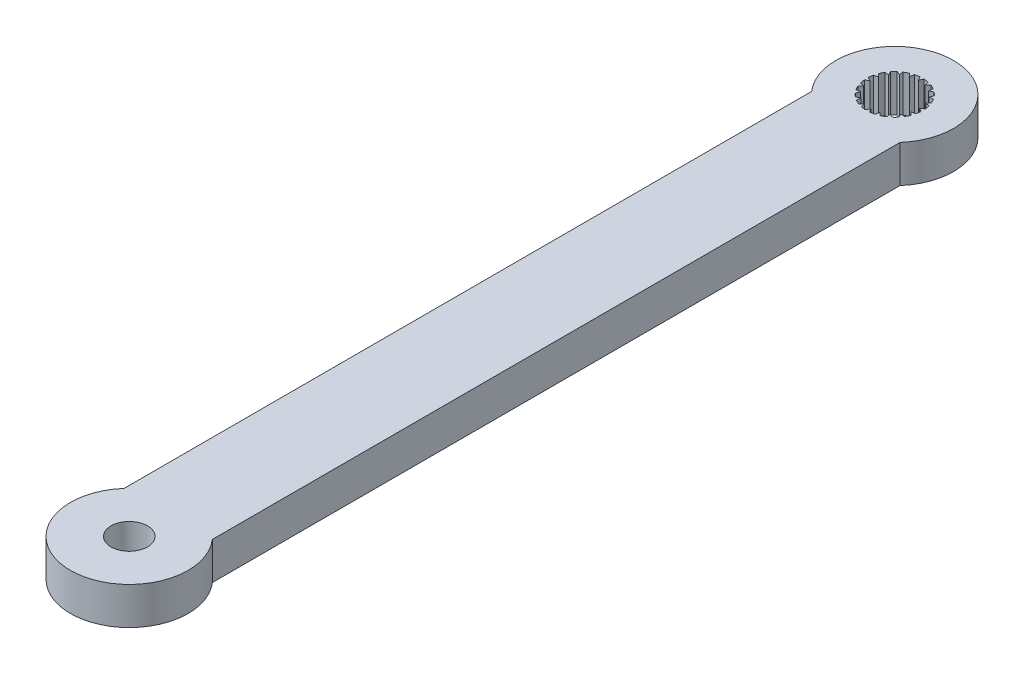
SolidWorks part; units mm, degrees
ref_plane "Front Plane" through (0, 0, 0) normal (0, 0, 1) x (1, 0, 0)
ref_plane "Top Plane" through (0, 0, 0) normal (0, 1, 0) x (1, 0, 0)
ref_plane "Right Plane" through (0, 0, 0) normal (1, 0, 0) x (0, 0, -1)
sketch "Sketch1" plane through (0, 0, 0) normal (0, 1, 0) x (1, 0, 0)
  line L1 (-3.75, -61.6928) -> (-3.75, -3.3072)
  line L4 (3.75, -61.6928) -> (3.75, -3.3072)
  line L5 (-3.75, -3.3072) -> (0, 0) construction
  line L6 (0, 0) -> (3.75, -3.3072) construction
  line L7 (-3.75, -3.3072) -> (3.75, -3.3072) construction
  line L48 (-1.178, -1.7007) -> (-1.2088, -2.0444)
  line L49 (-1.489, -1.8503) -> (-1.178, -1.7007)
  line L50 (-1.6459, -1.2535) -> (-1.7813, -1.5708)
  line L51 (-1.9879, -1.2996) -> (-1.6459, -1.2535)
  line L52 (-1.9527, -0.6835) -> (-2.1796, -0.9435)
  line L53 (-2.2922, -0.6217) -> (-1.9527, -0.6835)
  line L54 (-2.0684, -0.0466) -> (-2.3644, -0.2238)
  line L55 (-2.3721, 0.117) -> (-2.0684, -0.0466)
  line L56 (-1.9815, 0.5948) -> (-2.3179, 0.5178)
  line L57 (-2.2199, 0.8443) -> (-1.9815, 0.5948)
  line L58 (-1.7007, 1.178) -> (-2.0444, 1.2088)
  line L59 (-1.8503, 1.489) -> (-1.7007, 1.178)
  line L60 (-1.2535, 1.6459) -> (-1.5708, 1.7813)
  line L61 (-1.2996, 1.9879) -> (-1.2535, 1.6459)
  line L62 (-0.6835, 1.9527) -> (-0.9435, 2.1796)
  line L63 (-0.6217, 2.2922) -> (-0.6835, 1.9527)
  line L64 (-0.0466, 2.0684) -> (-0.2238, 2.3644)
  line L65 (0.117, 2.3721) -> (-0.0466, 2.0684)
  line L66 (0.5948, 1.9815) -> (0.5178, 2.3179)
  line L67 (0.8443, 2.2199) -> (0.5948, 1.9815)
  line L68 (1.178, 1.7007) -> (1.2088, 2.0444)
  line L69 (1.489, 1.8503) -> (1.178, 1.7007)
  line L70 (1.6459, 1.2535) -> (1.7813, 1.5708)
  line L71 (1.9879, 1.2996) -> (1.6459, 1.2535)
  line L72 (1.9527, 0.6835) -> (2.1796, 0.9435)
  line L73 (2.2922, 0.6217) -> (1.9527, 0.6835)
  line L74 (2.0684, 0.0466) -> (2.3644, 0.2238)
  line L75 (2.3721, -0.117) -> (2.0684, 0.0466)
  line L76 (1.9815, -0.5948) -> (2.3179, -0.5178)
  line L77 (2.2199, -0.8443) -> (1.9815, -0.5948)
  line L78 (1.7007, -1.178) -> (2.0444, -1.2088)
  line L79 (1.8503, -1.489) -> (1.7007, -1.178)
  line L80 (1.2535, -1.6459) -> (1.5708, -1.7813)
  line L81 (1.2996, -1.9879) -> (1.2535, -1.6459)
  line L82 (0.6835, -1.9527) -> (0.9435, -2.1796)
  line L83 (0.6217, -2.2922) -> (0.6835, -1.9527)
  line L84 (0.0466, -2.0684) -> (0.2238, -2.3644)
  line L85 (-0.117, -2.3721) -> (0.0466, -2.0684)
  line L86 (-0.5948, -1.9815) -> (-0.5178, -2.3179)
  line L87 (-0.8443, -2.2199) -> (-0.5948, -1.9815)
  line L88 (-1.178, -1.7007) -> (-1.2088, -2.0444)
  line L89 (-1.489, -1.8503) -> (-1.178, -1.7007)
  line L90 (-1.6459, -1.2535) -> (-1.7813, -1.5708)
  line L91 (-1.9879, -1.2996) -> (-1.6459, -1.2535)
  line L92 (-1.9527, -0.6835) -> (-2.1796, -0.9435)
  line L93 (-2.2922, -0.6217) -> (-1.9527, -0.6835)
  line L94 (-2.0684, -0.0466) -> (-2.3644, -0.2238)
  line L95 (-2.3721, 0.117) -> (-2.0684, -0.0466)
  line L96 (-1.9815, 0.5948) -> (-2.3179, 0.5178)
  line L97 (-2.2199, 0.8443) -> (-1.9815, 0.5948)
  line L98 (-1.7007, 1.178) -> (-2.0444, 1.2088)
  line L99 (-1.8503, 1.489) -> (-1.7007, 1.178)
  line L100 (-1.2535, 1.6459) -> (-1.5708, 1.7813)
  line L101 (-1.2996, 1.9879) -> (-1.2535, 1.6459)
  line L102 (-0.6835, 1.9527) -> (-0.9435, 2.1796)
  line L103 (-0.6217, 2.2922) -> (-0.6835, 1.9527)
  line L104 (-0.0466, 2.0684) -> (-0.2238, 2.3644)
  line L105 (0.117, 2.3721) -> (-0.0466, 2.0684)
  line L106 (0.5948, 1.9815) -> (0.5178, 2.3179)
  line L107 (0.8443, 2.2199) -> (0.5948, 1.9815)
  line L108 (1.178, 1.7007) -> (1.2088, 2.0444)
  line L109 (1.489, 1.8503) -> (1.178, 1.7007)
  line L110 (1.6459, 1.2535) -> (1.7813, 1.5708)
  line L111 (1.9879, 1.2996) -> (1.6459, 1.2535)
  line L112 (1.9527, 0.6835) -> (2.1796, 0.9435)
  line L113 (2.2922, 0.6217) -> (1.9527, 0.6835)
  line L114 (2.0684, 0.0466) -> (2.3644, 0.2238)
  line L115 (2.3721, -0.117) -> (2.0684, 0.0466)
  line L116 (1.9815, -0.5948) -> (2.3179, -0.5178)
  line L117 (2.2199, -0.8443) -> (1.9815, -0.5948)
  line L118 (1.7007, -1.178) -> (2.0444, -1.2088)
  line L119 (1.8503, -1.489) -> (1.7007, -1.178)
  line L120 (1.2535, -1.6459) -> (1.5708, -1.7813)
  line L121 (1.2996, -1.9879) -> (1.2535, -1.6459)
  line L122 (0.6835, -1.9527) -> (0.9435, -2.1796)
  line L123 (0.6217, -2.2922) -> (0.6835, -1.9527)
  line L124 (0.0466, -2.0684) -> (0.2238, -2.3644)
  line L125 (-0.117, -2.3721) -> (0.0466, -2.0684)
  line L126 (-0.5948, -1.9815) -> (-0.5178, -2.3179)
  line L127 (-0.8443, -2.2199) -> (-0.5948, -1.9815)
  arc A1 (3.75, -3.3072) -> (-3.75, -3.3072) centre (0, 0) ccw
  arc A2 (-3.75, -61.6928) -> (3.75, -61.6928) centre (0, -65) ccw
  circle A3 centre (0, -65) radius 1.55
  arc A25 (-1.7813, -1.5708) -> (-1.489, -1.8503) centre (0, 0) ccw
  arc A26 (-2.1796, -0.9435) -> (-1.9879, -1.2996) centre (0, 0) ccw
  arc A27 (-2.3644, -0.2238) -> (-2.2922, -0.6217) centre (0, 0) ccw
  arc A28 (-2.3179, 0.5178) -> (-2.3721, 0.117) centre (0, 0) ccw
  arc A29 (-2.0444, 1.2088) -> (-2.2199, 0.8443) centre (0, 0) ccw
  arc A30 (-1.5708, 1.7813) -> (-1.8503, 1.489) centre (0, 0) ccw
  arc A31 (-0.9435, 2.1796) -> (-1.2996, 1.9879) centre (0, 0) ccw
  arc A32 (-0.2238, 2.3644) -> (-0.6217, 2.2922) centre (0, 0) ccw
  arc A33 (0.5178, 2.3179) -> (0.117, 2.3721) centre (0, 0) ccw
  arc A34 (1.2088, 2.0444) -> (0.8443, 2.2199) centre (0, 0) ccw
  arc A35 (1.7813, 1.5708) -> (1.489, 1.8503) centre (0, 0) ccw
  arc A36 (2.1796, 0.9435) -> (1.9879, 1.2996) centre (0, 0) ccw
  arc A37 (2.3644, 0.2238) -> (2.2922, 0.6217) centre (0, 0) ccw
  arc A38 (2.3179, -0.5178) -> (2.3721, -0.117) centre (0, 0) ccw
  arc A39 (2.0444, -1.2088) -> (2.2199, -0.8443) centre (0, 0) ccw
  arc A40 (1.5708, -1.7813) -> (1.8503, -1.489) centre (0, 0) ccw
  arc A41 (0.9435, -2.1796) -> (1.2996, -1.9879) centre (0, 0) ccw
  arc A42 (0.2238, -2.3644) -> (0.6217, -2.2922) centre (0, 0) ccw
  arc A43 (-0.5178, -2.3179) -> (-0.117, -2.3721) centre (0, 0) ccw
  arc A44 (-1.2088, -2.0444) -> (-0.8443, -2.2199) centre (0, 0) ccw
  arc A45 (-1.7813, -1.5708) -> (-1.489, -1.8503) centre (0, 0) ccw
  arc A46 (-2.1796, -0.9435) -> (-1.9879, -1.2996) centre (0, 0) ccw
  arc A47 (-2.3644, -0.2238) -> (-2.2922, -0.6217) centre (0, 0) ccw
  arc A48 (-2.3179, 0.5178) -> (-2.3721, 0.117) centre (0, 0) ccw
  arc A49 (-2.0444, 1.2088) -> (-2.2199, 0.8443) centre (0, 0) ccw
  arc A50 (-1.5708, 1.7813) -> (-1.8503, 1.489) centre (0, 0) ccw
  arc A51 (-0.9435, 2.1796) -> (-1.2996, 1.9879) centre (0, 0) ccw
  arc A52 (-0.2238, 2.3644) -> (-0.6217, 2.2922) centre (0, 0) ccw
  arc A53 (0.5178, 2.3179) -> (0.117, 2.3721) centre (0, 0) ccw
  arc A54 (1.2088, 2.0444) -> (0.8443, 2.2199) centre (0, 0) ccw
  arc A55 (1.7813, 1.5708) -> (1.489, 1.8503) centre (0, 0) ccw
  arc A56 (2.1796, 0.9435) -> (1.9879, 1.2996) centre (0, 0) ccw
  arc A57 (2.3644, 0.2238) -> (2.2922, 0.6217) centre (0, 0) ccw
  arc A58 (2.3179, -0.5178) -> (2.3721, -0.117) centre (0, 0) ccw
  arc A59 (2.0444, -1.2088) -> (2.2199, -0.8443) centre (0, 0) ccw
  arc A60 (1.5708, -1.7813) -> (1.8503, -1.489) centre (0, 0) ccw
  arc A61 (0.9435, -2.1796) -> (1.2996, -1.9879) centre (0, 0) ccw
  arc A62 (0.2238, -2.3644) -> (0.6217, -2.2922) centre (0, 0) ccw
  arc A63 (-0.5178, -2.3179) -> (-0.117, -2.3721) centre (0, 0) ccw
  arc A64 (-1.2088, -2.0444) -> (-0.8443, -2.2199) centre (0, 0) ccw
  dimension "D3" = 10
  dimension "D6" = 10
  dimension "D5" = 3.1
  dimension "D1" = 0
  dimension "D4" = 7.5
  dimension "D7" = 65
extrude "Boss-Extrude1" add sketch "Sketch1" along normal blind 3.175
